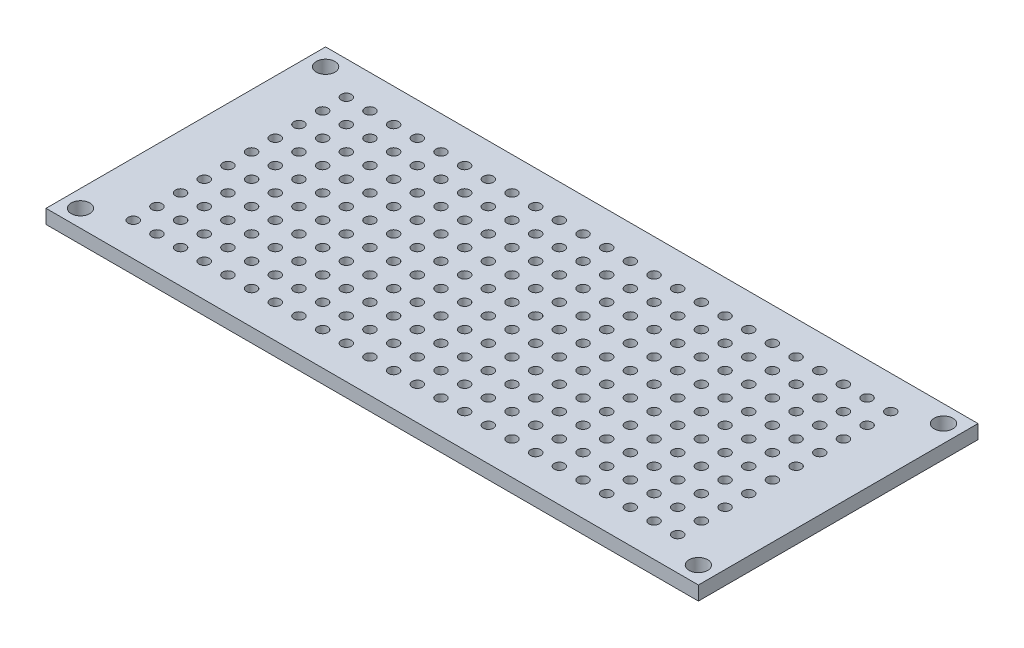
SolidWorks part; units mm, degrees
material "ABS"
ref_plane "Front" through (0, 0, 0) normal (0, 0, 1) x (1, 0, 0)
ref_plane "Top" through (0, 0, 0) normal (0, 1, 0) x (1, 0, 0)
ref_plane "Right" through (0, 0, 0) normal (1, 0, 0) x (0, 0, -1)
sketch "Sketch1" plane through (0, 0, 0) normal (0, 1, 0) x (1, 0, 0)
  line L1 (-35, 15) -> (35, 15)
  line L2 (-35, 15) -> (-35, -15)
  line L3 (-35, -15) -> (35, -15)
  line L4 (35, 15) -> (35, -15)
  line L5 (-35, 15) -> (35, -15) construction
  line L6 (-35, -15) -> (35, 15) construction
  point P0 (0, 0)
extrude "Boss-Extrude1" add sketch "Sketch1" along normal blind 1.5
sketch "Sketch2" plane through (0, 1.5, 0) normal (0, 1, 0) x (1, 0, 0)
  line L0 (0, 1.27) -> (0, 0) construction
  line L2 (0, 0) -> (1.27, 0) construction
  line L4 (0, 1.27) -> (1.27, 1.27) construction
  line L5 (1.27, 0) -> (1.27, 1.27) construction
  circle A0 centre (1.27, 1.27) radius 0.55
  circle A1 centre (3.81, 1.27) radius 0.55
  circle A2 centre (6.35, 1.27) radius 0.55
  circle A3 centre (8.89, 1.27) radius 0.55
  circle A4 centre (11.43, 1.27) radius 0.55
  circle A5 centre (13.97, 1.27) radius 0.55
  circle A6 centre (16.51, 1.27) radius 0.55
  circle A7 centre (19.05, 1.27) radius 0.55
  circle A8 centre (21.59, 1.27) radius 0.55
  circle A9 centre (24.13, 1.27) radius 0.55
  circle A10 centre (26.67, 1.27) radius 0.55
  circle A11 centre (29.21, 1.27) radius 0.55
  circle A12 centre (3.81, 3.81) radius 0.55
  circle A13 centre (6.35, 3.81) radius 0.55
  circle A14 centre (8.89, 3.81) radius 0.55
  circle A15 centre (11.43, 3.81) radius 0.55
  circle A16 centre (13.97, 3.81) radius 0.55
  circle A17 centre (16.51, 3.81) radius 0.55
  circle A18 centre (19.05, 3.81) radius 0.55
  circle A19 centre (21.59, 3.81) radius 0.55
  circle A20 centre (24.13, 3.81) radius 0.55
  circle A21 centre (26.67, 3.81) radius 0.55
  circle A22 centre (29.21, 3.81) radius 0.55
  circle A23 centre (3.81, 6.35) radius 0.55
  circle A24 centre (6.35, 6.35) radius 0.55
  circle A25 centre (8.89, 6.35) radius 0.55
  circle A26 centre (11.43, 6.35) radius 0.55
  circle A27 centre (13.97, 6.35) radius 0.55
  circle A28 centre (16.51, 6.35) radius 0.55
  circle A29 centre (19.05, 6.35) radius 0.55
  circle A30 centre (21.59, 6.35) radius 0.55
  circle A31 centre (24.13, 6.35) radius 0.55
  circle A32 centre (26.67, 6.35) radius 0.55
  circle A33 centre (29.21, 6.35) radius 0.55
  circle A34 centre (3.81, 8.89) radius 0.55
  circle A35 centre (6.35, 8.89) radius 0.55
  circle A36 centre (8.89, 8.89) radius 0.55
  circle A37 centre (11.43, 8.89) radius 0.55
  circle A38 centre (13.97, 8.89) radius 0.55
  circle A39 centre (16.51, 8.89) radius 0.55
  circle A40 centre (19.05, 8.89) radius 0.55
  circle A41 centre (21.59, 8.89) radius 0.55
  circle A42 centre (24.13, 8.89) radius 0.55
  circle A43 centre (26.67, 8.89) radius 0.55
  circle A44 centre (29.21, 8.89) radius 0.55
  circle A45 centre (3.81, 11.43) radius 0.55
  circle A46 centre (6.35, 11.43) radius 0.55
  circle A47 centre (8.89, 11.43) radius 0.55
  circle A48 centre (11.43, 11.43) radius 0.55
  circle A49 centre (13.97, 11.43) radius 0.55
  circle A50 centre (16.51, 11.43) radius 0.55
  circle A51 centre (19.05, 11.43) radius 0.55
  circle A52 centre (21.59, 11.43) radius 0.55
  circle A53 centre (24.13, 11.43) radius 0.55
  circle A54 centre (26.67, 11.43) radius 0.55
  circle A55 centre (29.21, 11.43) radius 0.55
  circle A56 centre (1.27, 3.81) radius 0.55
  circle A57 centre (1.27, 6.35) radius 0.55
  circle A58 centre (1.27, 8.89) radius 0.55
  circle A59 centre (1.27, 11.43) radius 0.55
  circle A60 centre (1.27, -11.43) radius 0.55
  circle A61 centre (1.27, -8.89) radius 0.55
  circle A62 centre (1.27, -6.35) radius 0.55
  circle A63 centre (1.27, -3.81) radius 0.55
  circle A64 centre (29.21, -11.43) radius 0.55
  circle A65 centre (26.67, -11.43) radius 0.55
  circle A66 centre (24.13, -11.43) radius 0.55
  circle A67 centre (21.59, -11.43) radius 0.55
  circle A68 centre (19.05, -11.43) radius 0.55
  circle A69 centre (16.51, -11.43) radius 0.55
  circle A70 centre (13.97, -11.43) radius 0.55
  circle A71 centre (11.43, -11.43) radius 0.55
  circle A72 centre (8.89, -11.43) radius 0.55
  circle A73 centre (6.35, -11.43) radius 0.55
  circle A74 centre (3.81, -11.43) radius 0.55
  circle A75 centre (29.21, -8.89) radius 0.55
  circle A76 centre (26.67, -8.89) radius 0.55
  circle A77 centre (24.13, -8.89) radius 0.55
  circle A78 centre (21.59, -8.89) radius 0.55
  circle A79 centre (19.05, -8.89) radius 0.55
  circle A80 centre (16.51, -8.89) radius 0.55
  circle A81 centre (13.97, -8.89) radius 0.55
  circle A82 centre (11.43, -8.89) radius 0.55
  circle A83 centre (8.89, -8.89) radius 0.55
  circle A84 centre (6.35, -8.89) radius 0.55
  circle A85 centre (3.81, -8.89) radius 0.55
  circle A86 centre (29.21, -6.35) radius 0.55
  circle A87 centre (26.67, -6.35) radius 0.55
  circle A88 centre (24.13, -6.35) radius 0.55
  circle A89 centre (21.59, -6.35) radius 0.55
  circle A90 centre (19.05, -6.35) radius 0.55
  circle A91 centre (16.51, -6.35) radius 0.55
  circle A92 centre (13.97, -6.35) radius 0.55
  circle A93 centre (11.43, -6.35) radius 0.55
  circle A94 centre (8.89, -6.35) radius 0.55
  circle A95 centre (6.35, -6.35) radius 0.55
  circle A96 centre (3.81, -6.35) radius 0.55
  circle A97 centre (29.21, -3.81) radius 0.55
  circle A98 centre (26.67, -3.81) radius 0.55
  circle A99 centre (24.13, -3.81) radius 0.55
  circle A100 centre (21.59, -3.81) radius 0.55
  circle A101 centre (19.05, -3.81) radius 0.55
  circle A102 centre (16.51, -3.81) radius 0.55
  circle A103 centre (13.97, -3.81) radius 0.55
  circle A104 centre (11.43, -3.81) radius 0.55
  circle A105 centre (8.89, -3.81) radius 0.55
  circle A106 centre (6.35, -3.81) radius 0.55
  circle A107 centre (3.81, -3.81) radius 0.55
  circle A108 centre (29.21, -1.27) radius 0.55
  circle A109 centre (26.67, -1.27) radius 0.55
  circle A110 centre (24.13, -1.27) radius 0.55
  circle A111 centre (21.59, -1.27) radius 0.55
  circle A112 centre (19.05, -1.27) radius 0.55
  circle A113 centre (16.51, -1.27) radius 0.55
  circle A114 centre (13.97, -1.27) radius 0.55
  circle A115 centre (11.43, -1.27) radius 0.55
  circle A116 centre (8.89, -1.27) radius 0.55
  circle A117 centre (6.35, -1.27) radius 0.55
  circle A118 centre (3.81, -1.27) radius 0.55
  circle A119 centre (1.27, -1.27) radius 0.55
  circle A120 centre (-1.27, -1.27) radius 0.55
  circle A121 centre (-3.81, -1.27) radius 0.55
  circle A122 centre (-6.35, -1.27) radius 0.55
  circle A123 centre (-8.89, -1.27) radius 0.55
  circle A124 centre (-11.43, -1.27) radius 0.55
  circle A125 centre (-13.97, -1.27) radius 0.55
  circle A126 centre (-16.51, -1.27) radius 0.55
  circle A127 centre (-19.05, -1.27) radius 0.55
  circle A128 centre (-21.59, -1.27) radius 0.55
  circle A129 centre (-24.13, -1.27) radius 0.55
  circle A130 centre (-26.67, -1.27) radius 0.55
  circle A131 centre (-29.21, -1.27) radius 0.55
  circle A132 centre (-3.81, -3.81) radius 0.55
  circle A133 centre (-6.35, -3.81) radius 0.55
  circle A134 centre (-8.89, -3.81) radius 0.55
  circle A135 centre (-11.43, -3.81) radius 0.55
  circle A136 centre (-13.97, -3.81) radius 0.55
  circle A137 centre (-16.51, -3.81) radius 0.55
  circle A138 centre (-19.05, -3.81) radius 0.55
  circle A139 centre (-21.59, -3.81) radius 0.55
  circle A140 centre (-24.13, -3.81) radius 0.55
  circle A141 centre (-26.67, -3.81) radius 0.55
  circle A142 centre (-29.21, -3.81) radius 0.55
  circle A143 centre (-3.81, -6.35) radius 0.55
  circle A144 centre (-6.35, -6.35) radius 0.55
  circle A145 centre (-8.89, -6.35) radius 0.55
  circle A146 centre (-11.43, -6.35) radius 0.55
  circle A147 centre (-13.97, -6.35) radius 0.55
  circle A148 centre (-16.51, -6.35) radius 0.55
  circle A149 centre (-19.05, -6.35) radius 0.55
  circle A150 centre (-21.59, -6.35) radius 0.55
  circle A151 centre (-24.13, -6.35) radius 0.55
  circle A152 centre (-26.67, -6.35) radius 0.55
  circle A153 centre (-29.21, -6.35) radius 0.55
  circle A154 centre (-3.81, -8.89) radius 0.55
  circle A155 centre (-6.35, -8.89) radius 0.55
  circle A156 centre (-8.89, -8.89) radius 0.55
  circle A157 centre (-11.43, -8.89) radius 0.55
  circle A158 centre (-13.97, -8.89) radius 0.55
  circle A159 centre (-16.51, -8.89) radius 0.55
  circle A160 centre (-19.05, -8.89) radius 0.55
  circle A161 centre (-21.59, -8.89) radius 0.55
  circle A162 centre (-24.13, -8.89) radius 0.55
  circle A163 centre (-26.67, -8.89) radius 0.55
  circle A164 centre (-29.21, -8.89) radius 0.55
  circle A165 centre (-3.81, -11.43) radius 0.55
  circle A166 centre (-6.35, -11.43) radius 0.55
  circle A167 centre (-8.89, -11.43) radius 0.55
  circle A168 centre (-11.43, -11.43) radius 0.55
  circle A169 centre (-13.97, -11.43) radius 0.55
  circle A170 centre (-16.51, -11.43) radius 0.55
  circle A171 centre (-19.05, -11.43) radius 0.55
  circle A172 centre (-21.59, -11.43) radius 0.55
  circle A173 centre (-24.13, -11.43) radius 0.55
  circle A174 centre (-26.67, -11.43) radius 0.55
  circle A175 centre (-29.21, -11.43) radius 0.55
  circle A176 centre (-1.27, -3.81) radius 0.55
  circle A177 centre (-1.27, -6.35) radius 0.55
  circle A178 centre (-1.27, -8.89) radius 0.55
  circle A179 centre (-1.27, -11.43) radius 0.55
  circle A180 centre (-1.27, 11.43) radius 0.55
  circle A181 centre (-1.27, 8.89) radius 0.55
  circle A182 centre (-1.27, 6.35) radius 0.55
  circle A183 centre (-1.27, 3.81) radius 0.55
  circle A184 centre (-29.21, 11.43) radius 0.55
  circle A185 centre (-26.67, 11.43) radius 0.55
  circle A186 centre (-24.13, 11.43) radius 0.55
  circle A187 centre (-21.59, 11.43) radius 0.55
  circle A188 centre (-19.05, 11.43) radius 0.55
  circle A189 centre (-16.51, 11.43) radius 0.55
  circle A190 centre (-13.97, 11.43) radius 0.55
  circle A191 centre (-11.43, 11.43) radius 0.55
  circle A192 centre (-8.89, 11.43) radius 0.55
  circle A193 centre (-6.35, 11.43) radius 0.55
  circle A194 centre (-3.81, 11.43) radius 0.55
  circle A195 centre (-29.21, 8.89) radius 0.55
  circle A196 centre (-26.67, 8.89) radius 0.55
  circle A197 centre (-24.13, 8.89) radius 0.55
  circle A198 centre (-21.59, 8.89) radius 0.55
  circle A199 centre (-19.05, 8.89) radius 0.55
  circle A200 centre (-16.51, 8.89) radius 0.55
  circle A201 centre (-13.97, 8.89) radius 0.55
  circle A202 centre (-11.43, 8.89) radius 0.55
  circle A203 centre (-8.89, 8.89) radius 0.55
  circle A204 centre (-6.35, 8.89) radius 0.55
  circle A205 centre (-3.81, 8.89) radius 0.55
  circle A206 centre (-29.21, 6.35) radius 0.55
  circle A207 centre (-26.67, 6.35) radius 0.55
  circle A208 centre (-24.13, 6.35) radius 0.55
  circle A209 centre (-21.59, 6.35) radius 0.55
  circle A210 centre (-19.05, 6.35) radius 0.55
  circle A211 centre (-16.51, 6.35) radius 0.55
  circle A212 centre (-13.97, 6.35) radius 0.55
  circle A213 centre (-11.43, 6.35) radius 0.55
  circle A214 centre (-8.89, 6.35) radius 0.55
  circle A215 centre (-6.35, 6.35) radius 0.55
  circle A216 centre (-3.81, 6.35) radius 0.55
  circle A217 centre (-29.21, 3.81) radius 0.55
  circle A218 centre (-26.67, 3.81) radius 0.55
  circle A219 centre (-24.13, 3.81) radius 0.55
  circle A220 centre (-21.59, 3.81) radius 0.55
  circle A221 centre (-19.05, 3.81) radius 0.55
  circle A222 centre (-16.51, 3.81) radius 0.55
  circle A223 centre (-13.97, 3.81) radius 0.55
  circle A224 centre (-11.43, 3.81) radius 0.55
  circle A225 centre (-8.89, 3.81) radius 0.55
  circle A226 centre (-6.35, 3.81) radius 0.55
  circle A227 centre (-3.81, 3.81) radius 0.55
  circle A228 centre (-29.21, 1.27) radius 0.55
  circle A229 centre (-26.67, 1.27) radius 0.55
  circle A230 centre (-24.13, 1.27) radius 0.55
  circle A231 centre (-21.59, 1.27) radius 0.55
  circle A232 centre (-19.05, 1.27) radius 0.55
  circle A233 centre (-16.51, 1.27) radius 0.55
  circle A234 centre (-13.97, 1.27) radius 0.55
  circle A235 centre (-11.43, 1.27) radius 0.55
  circle A236 centre (-8.89, 1.27) radius 0.55
  circle A237 centre (-6.35, 1.27) radius 0.55
  circle A238 centre (-3.81, 1.27) radius 0.55
  circle A239 centre (-1.27, 1.27) radius 0.55
  dimension "D1" = 12
  dimension "D2" = 5
extrude "Cut-Extrude1" cut sketch "Sketch2" against normal through all
sketch "Sketch3" plane through (0, 1.5, 0) normal (0, 1, 0) x (1, 0, 0)
  line L0 (-33.15, 15) -> (-33.15, 14.15) construction
  line L1 (35, 15) -> (-35, 15) construction
  line L2 (-33.15, 14.15) -> (-35, 14.15) construction
  line L3 (-35, 15) -> (-35, -15) construction
  line L4 (-35, 13.15) -> (-34.15, 13.15) construction
  line L5 (-34.15, 13.15) -> (-34.15, 15) construction
  line L6 (0, 15) -> (0, 0) construction
  line L7 (0, 0) -> (-35, 0) construction
  line L8 (-33.15, 13.15) -> (-33.15, -13.15) construction
  circle A0 centre (-33.15, 13.15) radius 1
  circle A2 centre (33.15, 13.15) radius 1
  circle A3 centre (-33.15, -13.15) radius 1
  circle A4 centre (33.15, -13.15) radius 1
extrude "Cut-Extrude2" cut sketch "Sketch3" against normal through all
